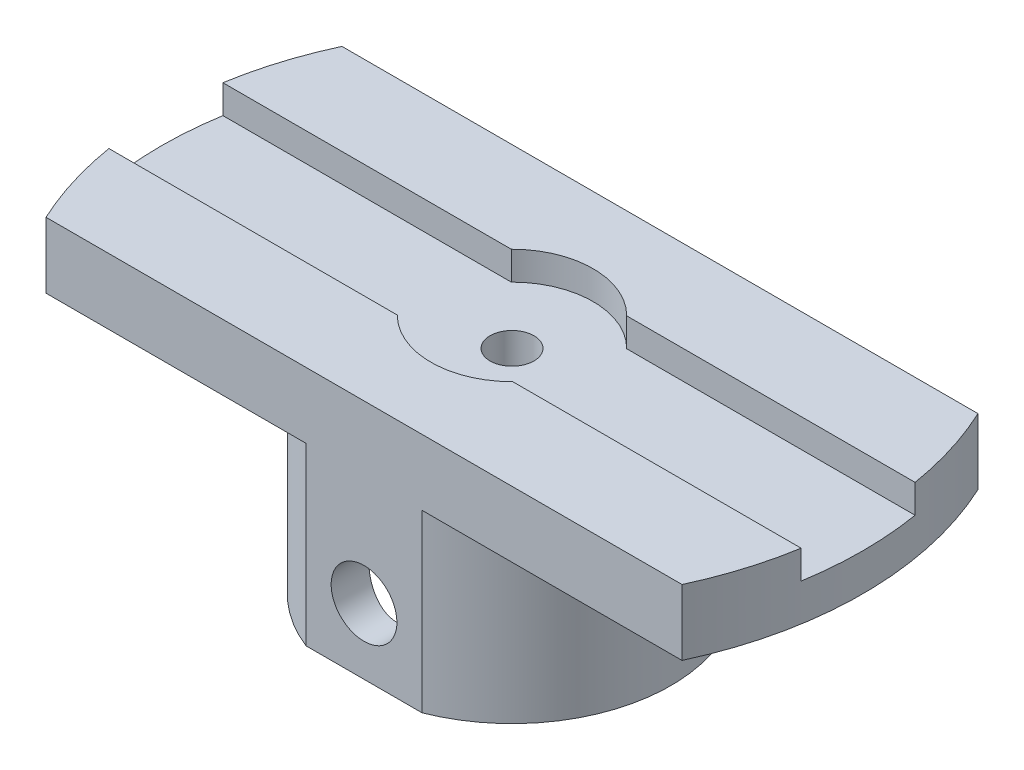
SolidWorks part; units mm, degrees
ref_plane "Front Plane" through (0, 0, 0) normal (0, 0, 1) x (1, 0, 0)
ref_plane "Top Plane" through (0, 0, 0) normal (0, 1, 0) x (1, 0, 0)
ref_plane "Right Plane" through (0, 0, 0) normal (1, 0, 0) x (0, 0, -1)
sketch "Sketch1" plane through (0, 0, 0) normal (0, 1, 0) x (1, 0, 0)
  circle A0 centre (0, 0) radius 16
  dimension "D1" = 32
extrude "Boss-Extrude1" add sketch "Sketch1" along normal blind 3
sketch "Sketch2" plane through (0, 3, 0) normal (0, 1, 0) x (1, 0, 0)
  line L0 (-16, 0) -> (16, 0) construction
  line L1 (-15.7873, 2.6) -> (-2.3431, 2.6)
  line L2 (-15.7873, -2.6) -> (-2.3431, -2.6)
  line L3 (2.3431, 2.6) -> (15.7873, 2.6)
  line L4 (2.3431, -2.6) -> (15.7873, -2.6)
  arc A0 (2.3431, 2.6) -> (-2.3431, 2.6) centre (0, 0) ccw
  circle A1 centre (0, 0) radius 16 construction
  arc A2 (-15.7873, 2.6) -> (-15.7873, -2.6) centre (0, 0) ccw
  arc A3 (15.7873, 2.6) -> (15.7873, -2.6) centre (0, 0) cw
  arc A4 (-2.3431, -2.6) -> (2.3431, -2.6) centre (0, 0) ccw
  dimension "D1" = 7
  dimension "D2" = 2.6
  dimension "D3" = 2.6
extrude "Cut-Extrude1" cut sketch "Sketch2" against normal blind 1.3
sketch "Sketch4" plane through (0, 0.3, 0) normal (0, -1, 0) x (1, 0, 0)
  circle A0 centre (0, 0) radius 1
  dimension "D1" = 2
extrude "Cut-Extrude3" cut sketch "Sketch4" against normal blind 2 and the other way blind 2
sketch "Sketch5" plane through (0, 0, 0) normal (0, -1, 0) x (1, 0, 0)
  circle A0 centre (0, 0) radius 5.25
  dimension "D1" = 10.5
extrude "Extrude-Thin1" add sketch "Sketch5" along normal blind 8 thin thin type one direction wall 2
sketch "Sketch6" plane through (0, 0, 0) normal (1, 0, 0) x (0, 0, -1)
  line L0 (-7.25, 0) -> (-7.25, -8) construction
  line L1 (-17.3243, 6.3885) -> (-6.75, 6.3885)
  line L2 (-17.3243, 6.3885) -> (-17.3243, -14.0665)
  line L3 (-17.3243, -14.0665) -> (-6.75, -14.0665)
  line L4 (-6.75, 6.3885) -> (-6.75, -14.0665)
  line L5 (16.2274, 6.3885) -> (6.75, 6.3885)
  line L6 (16.2274, 6.3885) -> (16.2274, -14.9699)
  line L7 (16.2274, -14.9699) -> (6.75, -14.9699)
  line L8 (6.75, 6.3885) -> (6.75, -14.9699)
  line L9 (7.25, -8) -> (7.25, 0) construction
  dimension "D1" = 0.5
  dimension "D2" = 0.5
extrude "Cut-Extrude4" cut sketch "Sketch6" against normal blind 100 and the other way blind 100
sketch "Sketch7" plane through (0, 0, -6.75) normal (0, 0, -1) x (-1, 0, 0)
  line L0 (2.6458, 0) -> (14.5065, 0) construction
  circle A0 centre (0, -5) radius 1.5
  dimension "D1" = 3
  dimension "D2" = 5
extrude "Cut-Extrude5" cut sketch "Sketch7" against normal blind 30
sketch "Sketch8" plane through (0, 3, 0) normal (0, 1, 0) x (1, 0, 0)
  circle A0 centre (0, 0) radius 3.7
  dimension "D1" = 7.4
extrude "Cut-Extrude6" cut sketch "Sketch8" against normal blind 1.3
